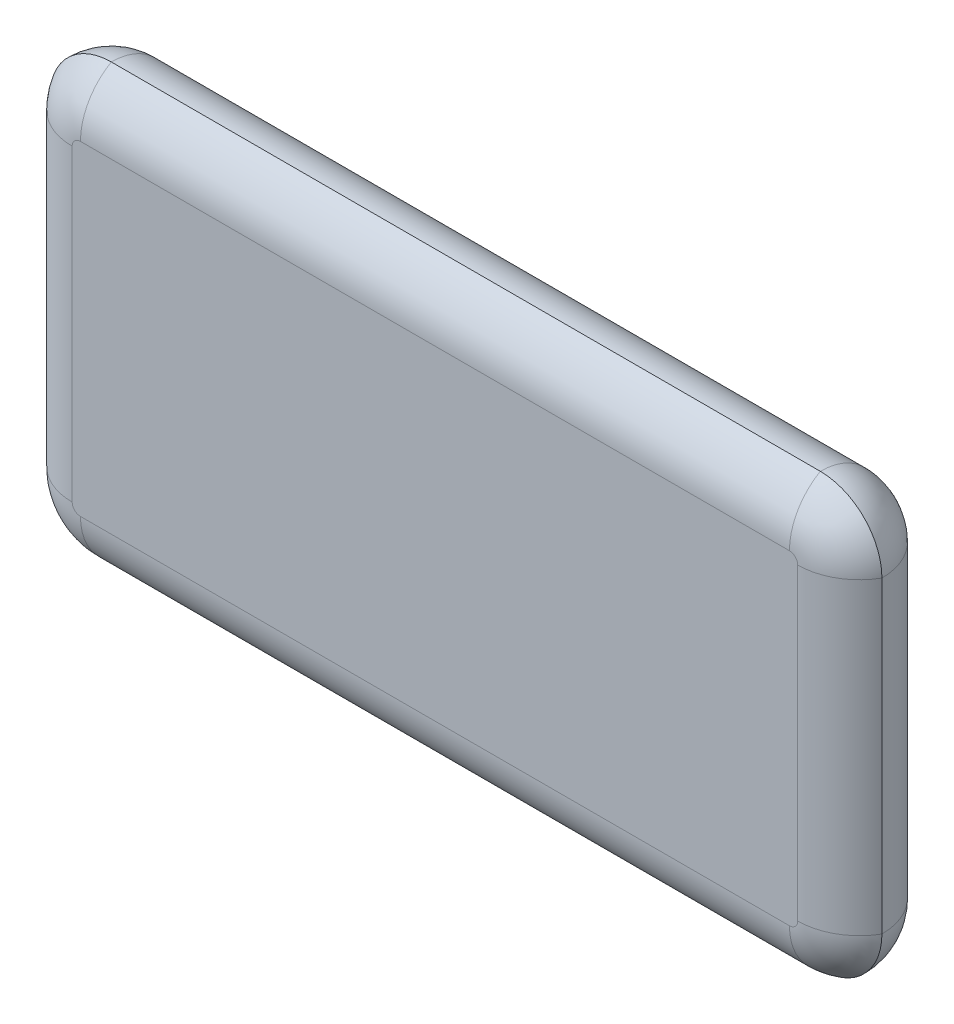
SolidWorks part; units mm, degrees
ref_plane "Front Plane" through (0, 0, 0) normal (0, 0, 1) x (1, 0, 0)
ref_plane "Top Plane" through (0, 0, 0) normal (0, 1, 0) x (1, 0, 0)
ref_plane "Right Plane" through (0, 0, 0) normal (1, 0, 0) x (0, 0, -1)
sketch "Sketch1" plane through (0, 0, 0) normal (0, 0, 1) x (1, 0, 0)
  line L5 (-49.0956, 47.3037) -> (85.9044, 47.3037)
  line L6 (-49.0956, 47.3037) -> (-49.0956, -22.6963)
  line L7 (-49.0956, -22.6963) -> (85.9044, -22.6963)
  line L8 (85.9044, 47.3037) -> (85.9044, -22.6963)
  dimension "D1" = 70
  dimension "D2" = 135
extrude "Boss-Extrude1" add sketch "Sketch1" along normal blind 15
fillet "Fillet2" radius 10 1 edges at (-49.0956, -22.6963, 7.5)
fillet "Fillet3" radius 10 1 edges at (-49.0956, 47.3037, 7.5)
fillet "Fillet4" radius 10 1 edges at (85.9044, 47.3037, 7.5)
fillet "Fillet5" radius 10 1 edges at (85.9044, -22.6963, 7.5)
fillet "Fillet12" radius 10 8 edges at (82.9755, 44.3748, 0) (82.9755, -19.7674, 0) (-46.1667, -19.7674, 0) (-46.1667, 44.3748, 0) (-49.0956, 12.3037, 0) (18.4044, -22.6963, 0) (85.9044, 12.3037, 0) (18.4044, 47.3037, 0)
fillet "Fillet13" radius 10 8 edges at (82.9755, 44.3748, 15) (82.9755, -19.7674, 15) (-46.1667, -19.7674, 15) (-46.1667, 44.3748, 15) (-49.0956, 12.3037, 15) (18.4044, -22.6963, 15) (85.9044, 12.3037, 15) (18.4044, 47.3037, 15)
